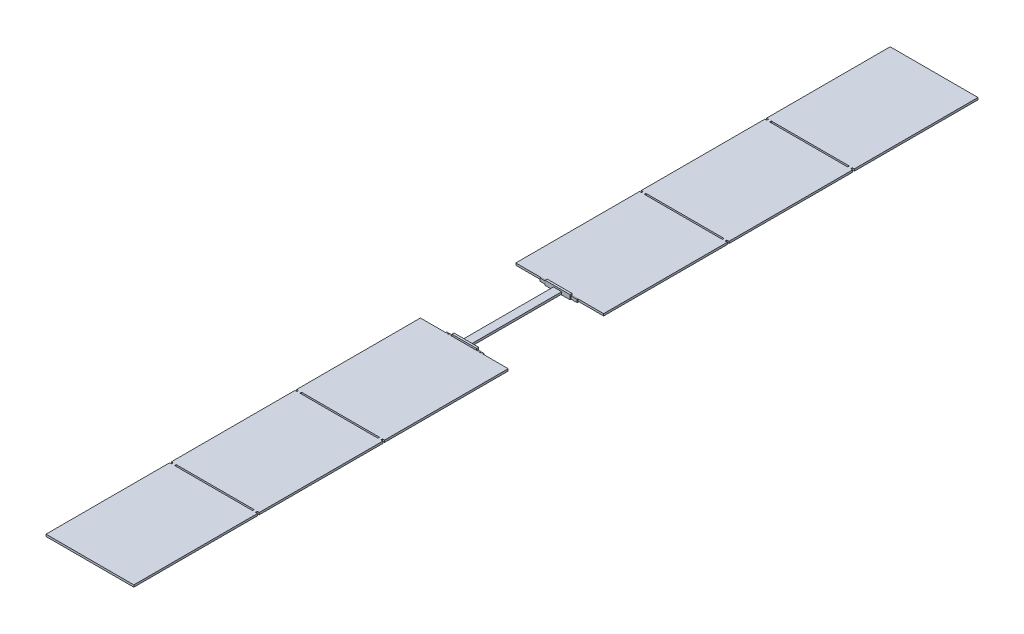
SolidWorks part; units mm, degrees
ref_plane "Piano frontale" through (0, 0, 0) normal (0, 0, 1) x (1, 0, 0)
ref_plane "Piano superiore" through (0, 0, 0) normal (0, 1, 0) x (1, 0, 0)
ref_plane "Piano destro" through (0, 0, 0) normal (1, 0, 0) x (0, 0, -1)
sketch "Schizzo2" plane through (0, 0, 0) normal (0, 1, 0) x (1, 0, 0)
  line L0 (-113.15, 106.65) -> (-113.15, -106.65)
  line L5 (-106.65, 113.15) -> (106.65, 113.15)
  line L6 (113.15, 106.65) -> (113.15, -106.65)
  line L7 (106.65, -113.15) -> (-106.65, -113.15)
  line L10 (-113.15, 106.65) -> (-106.65, 106.65)
  line L11 (-106.65, 113.15) -> (-106.65, 106.65)
  line L14 (-106.65, -113.15) -> (-106.65, -106.65)
  line L15 (-113.15, -106.65) -> (-106.65, -106.65)
  line L16 (113.15, -106.65) -> (106.65, -106.65)
  line L17 (106.65, -113.15) -> (106.65, -106.65)
  line L36 (106.65, 113.15) -> (106.65, 106.65)
  line L37 (106.65, 106.65) -> (113.15, 106.65)
extrude "Estrusione-Estrusione2" add sketch "Schizzo2" along normal blind 150 and the other way blind 150
sketch "Schizzo3" plane through (0, -150, 0) normal (0, -1, 0) x (1, 0, 0)
  line L1 (-106.65, 113.15) -> (-113.15, 113.15)
  line L2 (-106.65, 113.15) -> (-106.65, 106.65)
  line L3 (-106.65, 106.65) -> (-113.15, 106.65)
  line L4 (-113.15, 113.15) -> (-113.15, 106.65)
  line L5 (106.65, 113.15) -> (113.15, 113.15)
  line L6 (106.65, 113.15) -> (106.65, 106.65)
  line L7 (106.65, 106.65) -> (113.15, 106.65)
  line L8 (113.15, 113.15) -> (113.15, 106.65)
  line L9 (106.65, -106.65) -> (113.15, -106.65)
  line L10 (106.65, -106.65) -> (106.65, -113.15)
  line L11 (106.65, -113.15) -> (113.15, -113.15)
  line L12 (113.15, -106.65) -> (113.15, -113.15)
  line L13 (-106.65, -106.65) -> (-113.15, -106.65)
  line L14 (-106.65, -106.65) -> (-106.65, -113.15)
  line L15 (-106.65, -113.15) -> (-113.15, -113.15)
  line L16 (-113.15, -106.65) -> (-113.15, -113.15)
extrude "Estrusione-Estrusione3" add sketch "Schizzo3" along normal blind 3.3 and the other way blind 303.3
sketch "Schizzo11" plane through (0, 0, -113.15) normal (0, 0, -1) x (-1, 0, 0)
  line L0 (-106.65, 150) -> (106.65, 150) construction
  line L1 (-30, 143) -> (30, 143)
  line L2 (-30, 143) -> (-30, 139)
  line L3 (-30, 139) -> (30, 139)
  line L4 (30, 143) -> (30, 139)
  line L5 (-45, 139) -> (45, 139)
  line L6 (-45, 139) -> (-45, 132)
  line L7 (-45, 132) -> (45, 132)
  line L8 (45, 139) -> (45, 132)
  line L10 (-45, 135.5) -> (-43, 135.5)
  line L11 (-45, 135.5) -> (-45, 132)
  line L12 (-45, 132) -> (-43, 132)
  line L13 (-43, 135.5) -> (-43, 132)
  line L14 (-43, 133.75) -> (43, 133.75)
  line L15 (-43, 133.75) -> (-43, 132)
  line L16 (-43, 132) -> (43, 132)
  line L17 (0, 133.75) -> (0, 132)
  line L18 (43, 133.75) -> (43, 132)
  line L19 (45, 132) -> (43, 132)
  line L20 (43, 135.5) -> (43, 132)
  line L21 (45, 135.5) -> (43, 135.5)
  line L22 (45, 135.5) -> (45, 132)
  point P10 (0, 150)
  dimension "D1" = 7
  dimension "D2" = 4
  dimension "D3" = 60
  dimension "D4" = 30
  dimension "D5" = 0
  dimension "D6" = 90
  dimension "D7" = 45
  dimension "D8" = 7
  dimension "D9" = 2
extrude "Estrusione-Estrusione10" add sketch "Schizzo11" along normal blind 2.5 contours L1 L4 L3 L2
extrude "Estrusione-Estrusione11" add sketch "Schizzo11<5>" along normal blind 2.5 contours L21 L8 L5 L3 L6 L10 L13 L14 L20 region at (0, 136.4013, -113.15)
sketch "Schizzo11<5>" plane through (0, 0, -113.15) normal (0, 0, -1) x (-1, 0, 0) same geometry as "Schizzo11"
extrude "Estrusione-Estrusione12" add sketch "Schizzo11<8>" along normal blind 4.5 contours L18 L14 L17 L16 | L17 L14 L13 L7 | L13 L10 L6 L7 | L8 L21 L20 L18 L7 region at (44, 133.75, -113.15) region at (-44, 133.75, -113.15) region at (21.5, 132.875, -113.15) region at (-21.5, 132.875, -113.15)
sketch "Schizzo11<8>" plane through (0, 0, -113.15) normal (0, 0, -1) x (-1, 0, 0) same geometry as "Schizzo11"
sketch "Schizzo13" plane through (0, 0, -115.65) normal (0, 0, -1) x (-1, 0, 0)
  line L2 (-106.65, 138.75) -> (106.35, 138.75)
  line L3 (-106.65, 138.75) -> (-106.65, 133.75)
  line L4 (-106.65, 133.75) -> (106.35, 133.75)
  line L5 (106.35, 138.75) -> (106.35, 133.75)
  line L7 (-113.15, 153.3) -> (-113.15, -153.3) construction
  line L8 (-43, 133.75) -> (43, 133.75) construction
  dimension "D1" = 5
  dimension "D2" = 213
  dimension "D3" = 6.5
  dimension "D4" = 0
extrude "Estrusione-Estrusione13" add sketch "Schizzo13" along normal blind 300
sketch "Schizzo15" plane through (0, 0, -415.65) normal (0, 0, -1) x (-1, 0, 0)
  line L0 (106.35, 138.75) -> (-106.65, 138.75) construction
  line L1 (-101.65, 138.75) -> (-94.65, 138.75)
  line L2 (-101.65, 138.75) -> (-101.65, 133.75)
  line L3 (-101.65, 133.75) -> (-94.65, 133.75)
  line L4 (-94.65, 138.75) -> (-94.65, 133.75)
  line L5 (-106.65, 133.75) -> (106.35, 133.75) construction
  line L6 (-106.65, 138.75) -> (-106.65, 133.75) construction
  line L9 (101.65, 133.75) -> (94.65, 133.75)
  line L10 (94.65, 138.75) -> (94.65, 133.75)
  line L11 (101.65, 138.75) -> (94.65, 138.75)
  line L12 (101.65, 138.75) -> (101.65, 133.75)
  dimension "D1" = 5
  dimension "D2" = 7
extrude "Estrusione-Estrusione14" add sketch "Schizzo15" along normal blind 4
sketch "Schizzo16" plane through (0, 0, -419.65) normal (0, 0, -1) x (-1, 0, 0)
  line L1 (-106.65, 138.75) -> (106.35, 138.75)
  line L2 (-106.65, 138.75) -> (-106.65, 133.75)
  line L3 (-106.65, 133.75) -> (106.35, 133.75)
  line L4 (106.35, 138.75) -> (106.35, 133.75)
extrude "Estrusione-Estrusione15" add sketch "Schizzo16" along normal blind 300
pattern_linear "Ripetizione a L2" count 2 spacing 304 along (0, 0, -1) of "Estrusione-Estrusione15", "Estrusione-Estrusione14"
sketch3d "Schizzo3D1" plane through (0, 0, 0) normal (0, 0, 1) x (1, 0, 0)
mirror "Specchia2" about plane through (0, 0, 0) normal (0, 0, 1) of "Estrusione-Estrusione10", "Estrusione-Estrusione11", "Estrusione-Estrusione12", "Estrusione-Estrusione13", "Estrusione-Estrusione14", "Estrusione-Estrusione15", "Ripetizione a L2"
sketch "Schizzo17" plane through (0, 150, 0) normal (0, 1, 0) x (1, 0, 0)
  line L0 (-106.65, -113.15) -> (106.65, -113.15) construction
  line L1 (-113.15, 113.15) -> (-30, 113.15)
  line L2 (-113.15, 113.15) -> (-113.15, -113.15)
  line L3 (-113.15, -113.15) -> (-30, -113.15)
  line L4 (-30, 113.15) -> (-30, -113.15)
  line L5 (113.15, 113.15) -> (30, 113.15)
  line L6 (113.15, 113.15) -> (113.15, -113.15)
  line L7 (113.15, -113.15) -> (30, -113.15)
  line L8 (30, 113.15) -> (30, -113.15)
  line L9 (45, -113.15) -> (30, -113.15) construction
extrude "Taglio-Estrusione1" cut sketch "Schizzo17" against normal blind 404
delete or keep bodies "Corpo-Elimina/Mantieni 1" type delete bodies bodies 131 133 134 132
sketch "Schizzo18" plane through (30, 0, 0) normal (1, 0, 0) x (0, 0, -1)
  line L1 (-113.15, 150) -> (113.15, 150)
  line L2 (-113.15, 150) -> (-113.15, 143)
  line L3 (-113.15, 143) -> (113.15, 143)
  line L4 (113.15, 150) -> (113.15, 143)
  line L5 (113.15, -150) -> (-113.15, -150)
  line L6 (113.15, -150) -> (113.15, 132)
  line L7 (113.15, 132) -> (-113.15, 132)
  line L8 (-113.15, -150) -> (-113.15, 132)
extrude "Taglio-Estrusione2" cut sketch "Schizzo18" against normal blind 404
sketch "Schizzo23" plane through (30, 0, 0) normal (1, 0, 0) x (0, 0, -1)
  line L0 (115.65, 143) -> (-115.65, 143) construction
  line L1 (-110.65, 143) -> (110.65, 143)
  line L2 (-110.65, 143) -> (-110.65, 139)
  line L3 (-110.65, 139) -> (110.65, 139)
  line L4 (110.65, 143) -> (110.65, 139)
  line L5 (113.15, 132) -> (-113.15, 132) construction
  line L6 (-110.65, 132) -> (110.65, 132)
  line L7 (-110.65, 132) -> (-110.65, 133.75)
  line L8 (-110.65, 133.75) -> (110.65, 133.75)
  line L9 (110.65, 132) -> (110.65, 133.75)
  line L10 (-115.65, 143) -> (-115.65, 139) construction
  line L11 (115.65, 143) -> (115.65, 139) construction
  dimension "D1" = 5
  dimension "D2" = 5
  dimension "D3" = 5
  dimension "D4" = 5
  dimension "D5" = 1.75
  dimension "D6" = 4
extrude "Taglio-Estrusione7" cut sketch "Schizzo23" against normal blind 404
sketch "Schizzo24" plane through (0, 139, 0) normal (0, 1, 0) x (1, 0, 0)
  line L0 (-30, -110.65) -> (30, -110.65) construction
  line L1 (-30, 110.65) -> (-10, 110.65)
  line L2 (-30, 110.65) -> (-30, -110.65)
  line L3 (-30, -110.65) -> (-10, -110.65)
  line L4 (-10, 110.65) -> (-10, -110.65)
  line L5 (30, 110.65) -> (-30, 110.65) construction
  line L6 (30, -110.65) -> (10, -110.65)
  line L7 (30, -110.65) -> (30, 110.65)
  line L8 (30, 110.65) -> (10, 110.65)
  line L9 (10, -110.65) -> (10, 110.65)
  dimension "D1" = 20
  dimension "D2" = 20
extrude "Taglio-Estrusione8" cut sketch "Schizzo24" against normal blind 404
